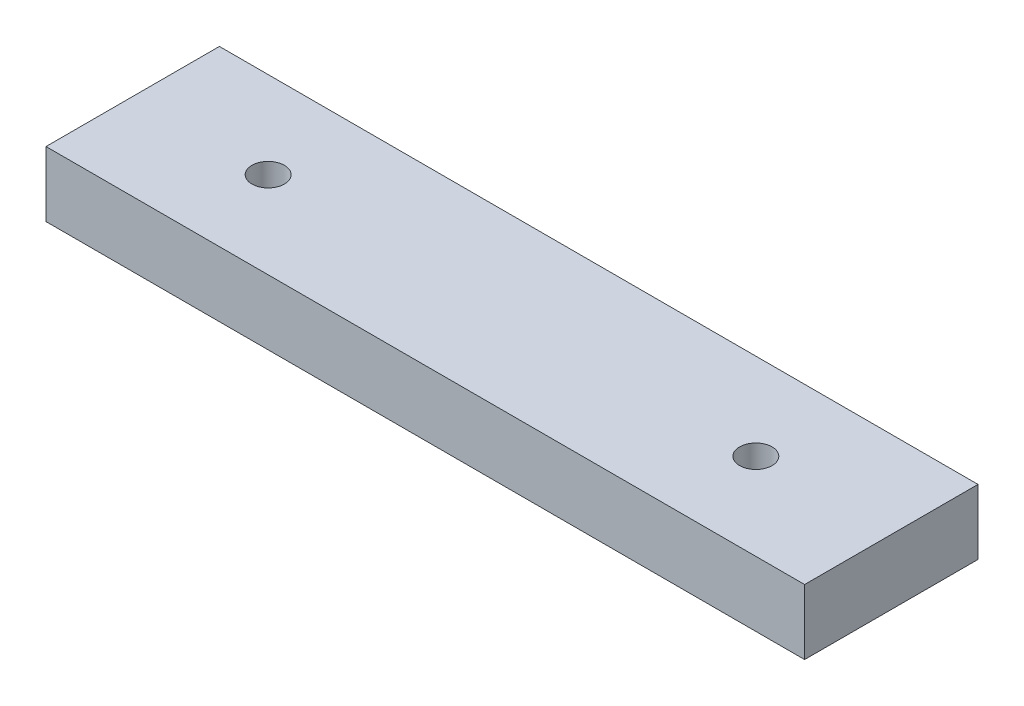
SolidWorks part; units mm, degrees
ref_plane "前基準面" through (0, 0, 0) normal (0, 0, 1) x (1, 0, 0)
ref_plane "上基準面" through (0, 0, 0) normal (0, 1, 0) x (1, 0, 0)
ref_plane "右基準面" through (0, 0, 0) normal (1, 0, 0) x (0, 0, -1)
sketch "草圖1" plane through (0, 0, 0) normal (0, 1, 0) x (1, 0, 0)
  line L1 (35, 8) -> (-35, 8)
  line L2 (35, 8) -> (35, -8)
  line L3 (35, -8) -> (-35, -8)
  line L4 (-35, 8) -> (-35, -8)
  line L5 (0, -8) -> (0, 8) construction
  line L6 (35, 0) -> (-35, 0) construction
  circle A0 centre (-22.5, 0) radius 1.5
  circle A1 centre (22.5, 0) radius 1.5
  point P0 (0, 0)
  dimension "D3" = 3
  dimension "D1" = 70
  dimension "D2" = 16
  dimension "D4" = 45
  dimension "D5" = 12.5
extrude "填料-伸長1" add sketch "草圖1" along normal blind 6
